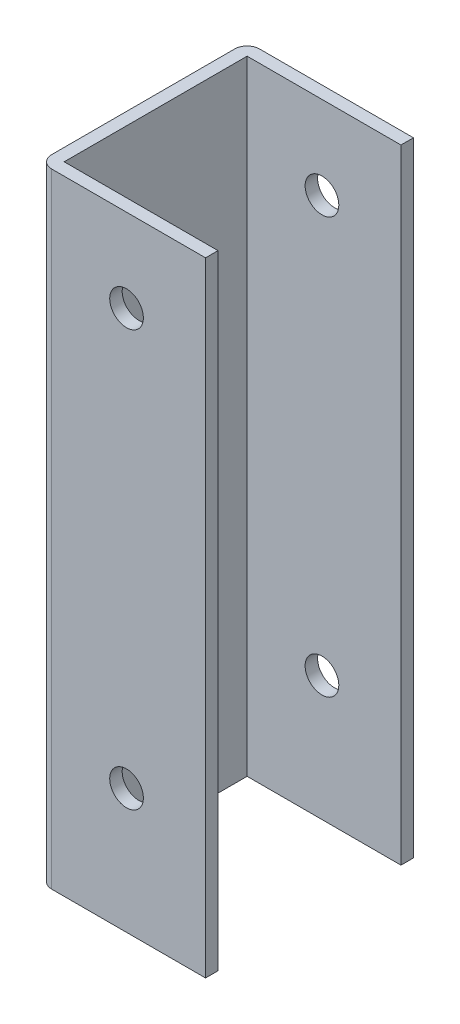
SolidWorks part; units mm, degrees
ref_plane "Спереди" through (0, 0, 0) normal (0, 0, 1) x (1, 0, 0)
ref_plane "Сверху" through (0, 0, 0) normal (0, 1, 0) x (1, 0, 0)
ref_plane "Справа" through (0, 0, 0) normal (1, 0, 0) x (0, 0, -1)
sketch "Эскиз1" plane through (0, 0, 0) normal (0, 1, 0) x (1, 0, 0)
  line L1 (-37, 25) -> (37, 25)
  line L2 (-40, 22) -> (-40, -22)
  line L3 (-37, -25) -> (37, -25)
  line L4 (40, 22) -> (40, -22)
  line L5 (-40, 25) -> (40, -25) construction
  line L6 (-40, -25) -> (40, 25) construction
  arc A0 (-37, 25) -> (-40, 22) centre (-37, 22) ccw
  arc A1 (-40, -22) -> (-37, -25) centre (-37, -22) ccw
  arc A2 (37, -25) -> (40, -22) centre (37, -22) ccw
  arc A3 (37, 25) -> (40, 22) centre (37, 22) cw
  point P0 (0, 0)
  dimension "D1" = 3
extrude "Вытянуть-Тонкостенный1" add sketch "Эскиз1" along normal blind 150 thin thin type one direction reverse wall 3
sketch "Эскиз2" plane through (0, 150, 0) normal (0, 1, 0) x (1, 0, 0)
  line L1 (0, -27.4206) -> (41.1465, -27.4206)
  line L2 (0, -27.4206) -> (0, 30.9728)
  line L3 (0, 30.9728) -> (41.1465, 30.9728)
  line L4 (41.1465, -27.4206) -> (41.1465, 30.9728)
  point P4 (0, -25)
  point P5 (0, -27.4206)
  point P7 (0, -25)
  point P8 (0, 0)
extrude "Вырез-Вытянуть1" cut sketch "Эскиз2" against normal through all
sketch "Эскиз3" plane through (0, 0, -25) normal (0, 0, -1) x (-1, 0, 0)
  circle A0 centre (19, 130) radius 4.05
  circle A1 centre (19, 30) radius 4.05
  dimension "D1" = 2
extrude "Вырез-Вытянуть2" cut sketch "Эскиз3" against normal through all
